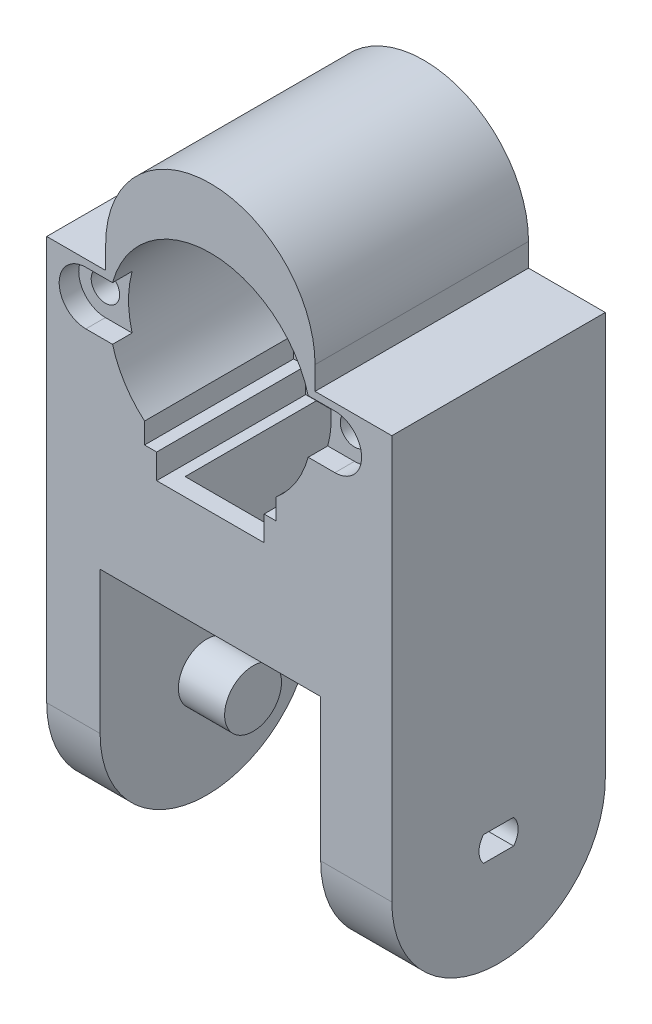
SolidWorks part; units mm, degrees
ref_plane "Front Plane" through (0, 0, 0) normal (0, 0, 1) x (1, 0, 0)
ref_plane "Top Plane" through (0, 0, 0) normal (0, 1, 0) x (1, 0, 0)
ref_plane "Right Plane" through (0, 0, 0) normal (1, 0, 0) x (0, 0, -1)
sketch "Sketch2" plane through (0, 0, 0) normal (0, 0, 1) x (1, 0, 0)
  line L0 (-7.55, 18.2411) -> (-7.55, 14.75)
  line L1 (-7.55, 14.75) -> (7.55, 14.75)
  line L2 (7.55, 14.75) -> (7.55, 18.2411)
  line L3 (7.55, 18.2411) -> (9.25, 18.2411)
  line L4 (9.25, 18.2411) -> (9.25, 21.1603)
  line L5 (-7.55, 18.2411) -> (-9.25, 18.2411)
  line L6 (-9.25, 18.2411) -> (-9.25, 21.1603)
  line L7 (-14.7095, 40) -> (-23, 40)
  line L8 (-23, 40) -> (-23, 0)
  line L10 (14.7095, 40) -> (23, 40)
  line L11 (23, 40) -> (23, 0)
  line L13 (-23, 0) -> (23, 0)
  arc A0 (14.7095, 40) -> (-14.7095, 40) centre (0, 40) ccw
  arc A4 (9.25, 21.1603) -> (-9.25, 21.1603) centre (0, 32) ccw
  point P6 (0, 14.75)
  point P15 (0, 0)
  dimension "D1" = 8.2905
  dimension "D12" = 3.4911
  dimension "D16" = 14.25
  dimension "D17" = 14.7095
  dimension "D2" = 8.2905
  dimension "D3" = 25.25
  dimension "D4" = 40
  dimension "D5" = 0
  dimension "D6" = 0
  dimension "D7" = 46
  dimension "D9" = 2.9191
  dimension "D10" = 1.7
  dimension "D11" = 1.7
  dimension "D13" = 15.1
  dimension "D14" = 2.9191
  dimension "D15" = 3.4911
extrude "Boss-Extrude1" add sketch "Sketch2" along normal blind 20.95
sketch "Sketch3" plane through (0, 0, 0) normal (0, 0, 1) x (1, 0, 0)
  line L7 (-14.7095, 40) -> (-23, 40)
  line L8 (-23, 40) -> (-23, 0)
  line L9 (14.7095, 40) -> (23, 40)
  line L10 (23, 40) -> (23, 0)
  line L11 (-23, 0) -> (23, 0)
  line L12 (23, 40) -> (14.7095, 40) construction
  line L13 (-23, 40) -> (-23, 0) construction
  line L17 (-23, 0) -> (23, 0) construction
  line L19 (23, 0) -> (23, 40) construction
  arc A0 (14.7095, 40) -> (-14.7095, 40) centre (0, 40) ccw
  arc A1 (14.7095, 40) -> (-14.7095, 40) centre (0, 40) ccw construction
  dimension "D1" = 0
extrude "Boss-Extrude2" add sketch "Sketch3" against normal blind 9.05
sketch "Sketch6" plane through (0, 0, 20.95) normal (0, 0, 1) x (1, 0, 0)
  line L0 (-14.7095, 40) -> (-23, 40) construction
  line L1 (-23, 40) -> (-23, 0) construction
  line L2 (23, 40) -> (14.7095, 40) construction
  line L3 (23, 0) -> (23, 40) construction
  circle A0 centre (-17.5, 32) radius 2
  circle A1 centre (17.5, 32) radius 2
  dimension "D1" = 8
  dimension "D2" = 5.5
  dimension "D3" = 4
  dimension "D4" = 8
  dimension "D5" = 5.5
  dimension "D6" = 4
extrude "Cut-Extrude2" cut sketch "Sketch6" against normal blind 10
sketch "Sketch7" plane through (0, 0, 20.95) normal (0, 0, 1) x (1, 0, 0)
  line L0 (-17.5, 32) -> (17.5, 32) construction
  line L3 (-17.5, 35.75) -> (17.5, 35.75)
  line L4 (-17.5, 28.25) -> (17.5, 28.25)
  arc A2 (-17.5, 35.75) -> (-17.5, 28.25) centre (-17.5, 32) ccw
  arc A3 (17.5, 28.25) -> (17.5, 35.75) centre (17.5, 32) ccw
  circle A4 centre (-17.5, 32) radius 2 construction
  circle A5 centre (-17.5, 32) radius 2 construction
  circle A6 centre (17.5, 32) radius 2 construction
  point P2 (0, 32)
  dimension "D2" = 7.5
  dimension "D3" = 1.75
  dimension "D4" = 1.75
  dimension "D1" = 3.75
extrude "Cut-Extrude3" cut sketch "Sketch7" against normal blind 2.75
sketch "Sketch8" plane through (0, 0, 20.95) normal (0, 0, 1) x (1, 0, 0)
  line L0 (-14.7095, 40) -> (-23, 40) construction
  line L1 (-14.7095, 40) -> (-23, 40)
  line L2 (-14.7095, 40) -> (-14.7095, 36.75)
  line L3 (-14.7095, 36.75) -> (-23, 36.75)
  line L4 (-23, 40) -> (-23, 36.75)
  line L5 (14.7095, 40) -> (23, 40)
  line L6 (14.7095, 40) -> (14.7095, 36.75)
  line L7 (14.7095, 36.75) -> (23, 36.75)
  line L8 (23, 40) -> (23, 36.75)
  line L9 (-23, 40) -> (-23, 0) construction
  line L10 (-13.7477, 35.75) -> (-17.5, 35.75) construction
  line L11 (17.5, 35.75) -> (13.7477, 35.75) construction
  line L12 (23, 0) -> (23, 40) construction
  line L13 (23, 40) -> (14.7095, 40) construction
  dimension "D2" = 1
  dimension "D3" = 1
extrude "Cut-Extrude4" cut sketch "Sketch8" along normal through all both and the other way through all
sketch "Sketch11" plane through (0, 0, -9.05) normal (0, 0, -1) x (-1, 0, 0)
  circle A0 centre (0, 40) radius 11.15
  arc A1 (14.7095, 40) -> (-14.7095, 40) centre (0, 40) ccw construction
  dimension "D1" = 22.3
extrude "Bearing Hole" cut sketch "Sketch11" against normal blind 7.3
sketch "Sketch9" plane through (0, 14.75, -19.25) normal (0, 1, 0) x (-1, 0, 0)
  line L0 (7.55, 40.2) -> (-7.55, 40.2) construction
  line L1 (-6.05, 37.7) -> (6.05, 37.7)
  line L2 (-6.05, 37.7) -> (-6.05, 16.2)
  line L3 (-6.05, 16.2) -> (6.05, 16.2)
  line L4 (6.05, 37.7) -> (6.05, 16.2)
  line L8 (-7.55, 40.2) -> (-7.55, 19.25) construction
  line L9 (7.55, 40.2) -> (7.55, 19.25) construction
  line L10 (7.55, 10.2) -> (-7.55, 10.2) construction
  dimension "D1" = 2.5
  dimension "D2" = 1.5
  dimension "D3" = 1.5
  dimension "D4" = 6
extrude "Wire Hole" cut sketch "Sketch9" against normal through all
sketch "Sketch12" plane through (0, 0, 0) normal (0, -1, 0) x (1, 0, 0)
  line L0 (-23, -9.05) -> (23, -9.05) construction
  line L1 (-23, -9.05) -> (23, -9.05)
  line L2 (-23, -9.05) -> (-23, 20.95)
  line L3 (-23, 20.95) -> (23, 20.95)
  line L4 (23, -9.05) -> (23, 20.95)
  line L5 (-23, 20.95) -> (23, 20.95) construction
  line L7 (-23, 20.95) -> (-23, -9.05) construction
  point P4 (0, -9.05)
  dimension "D1" = 0
  dimension "D2" = 0
  dimension "D3" = 0
  dimension "D4" = 0
extrude "Boss-Extrude3" add sketch "Sketch12" along normal blind 0.0001
sketch "Sketch13" plane through (23, 0, 0) normal (1, 0, 0) x (0, 0, -1)
  line L0 (-20.95, -0.0001) -> (-20.95, -20.0001)
  line L1 (9.05, -0.0001) -> (9.05, -20.0001)
  line L6 (9.05, 36.75) -> (-20.95, 36.75)
  line L7 (-20.95, 36.75) -> (-20.95, -0.0001)
  line L8 (-20.95, -0.0001) -> (9.05, -0.0001)
  line L9 (9.05, -0.0001) -> (9.05, 36.75)
  line L12 (-20.95, -0.0001) -> (9.05, -0.0001)
  arc A0 (-20.95, -20.0001) -> (9.05, -20.0001) centre (-5.95, -20.0001) ccw
  dimension "D1" = 0
  dimension "D2" = 20
extrude "Boss-Extrude4" add sketch "Sketch13" against normal blind 7.5
sketch "Sketch14" plane through (-23, 0, 0) normal (-1, 0, 0) x (0, 0, 1)
  line L0 (-9.05, -20.0001) -> (-9.05, -0.0001)
  line L1 (-9.05, -0.0001) -> (20.95, -0.0001)
  line L2 (20.95, -0.0001) -> (20.95, -20.0001)
  arc A0 (-9.05, -20.0001) -> (20.95, -20.0001) centre (5.95, -20.0001) ccw
extrude "Boss-Extrude5" add sketch "Sketch14" against normal blind 7.5
sketch "Sketch21" plane through (23, 0, 0) normal (1, 0, 0) x (0, 0, -1)
  line L0 (-20.95, -20.0001) -> (-20.95, 36.75)
  line L1 (-20.95, 36.75) -> (9.05, 36.75)
  line L2 (9.05, 36.75) -> (9.05, -20.0001)
  arc A0 (-20.95, -20.0001) -> (9.05, -20.0001) centre (-5.95, -20.0001) ccw
extrude "Boss-Extrude9" add sketch "Sketch21" along normal blind 2.5
sketch "Sketch15" plane through (-23, 0, 0) normal (-1, 0, 0) x (0, 0, 1)
  circle A0 centre (5.95, -20.0001) radius 4
extrude "Cut-Extrude5" cut sketch "Sketch15" against normal through all
sketch "Sketch17" plane through (25.5, 0, -23) normal (-1, 0, 0) x (0, 0, 1)
  line L4 (26.8287, -18.2501) -> (31.0713, -18.2501)
  line L5 (26.8287, -21.7501) -> (31.0713, -21.7501)
  arc A10 (26.8287, -18.2501) -> (26.8287, -21.7501) centre (28.95, -20.0001) ccw
  arc A11 (31.0713, -18.2501) -> (31.0713, -21.7501) centre (28.95, -20.0001) cw
  circle A14 centre (28.95, -20.0001) radius 6.1696
  arc A16 (13.95, -20.0001) -> (43.95, -20.0001) centre (28.95, -20.0001) ccw construction
  circle A17 centre (28.95, -20.0001) radius 4 construction
  point P11 (28.95, -35.0001)
  dimension "D1" = 4.2426
  dimension "D2" = 4.2426
  dimension "D3" = 2.75
  dimension "D4" = 2.75
extrude "Boss-Extrude6" add sketch "Sketch17" along normal up to surface (10 mm away) up to face at (15.5, -20.0001, 1.95)
sketch "Sketch18" plane through (-23, 0, 0) normal (-1, 0, 0) x (0, 0, 1)
  circle A0 centre (5.95, -20.0001) radius 4
  dimension "D1" = 8
extrude "Boss-Extrude7" add sketch "Sketch18" against normal offset from surface (14 mm away) 6.5 up to face at (-15.5, -24.0001, 5.95) offset beyond the face yes
sketch "Sketch19" plane through (15.5, 0, 0) normal (-1, 0, 0) x (0, 0, 1)
  circle A0 centre (5.95, -20.0001) radius 4.675
  dimension "D1" = 9.35
extrude "Cut-Extrude6" cut sketch "Sketch19" against normal blind 2
